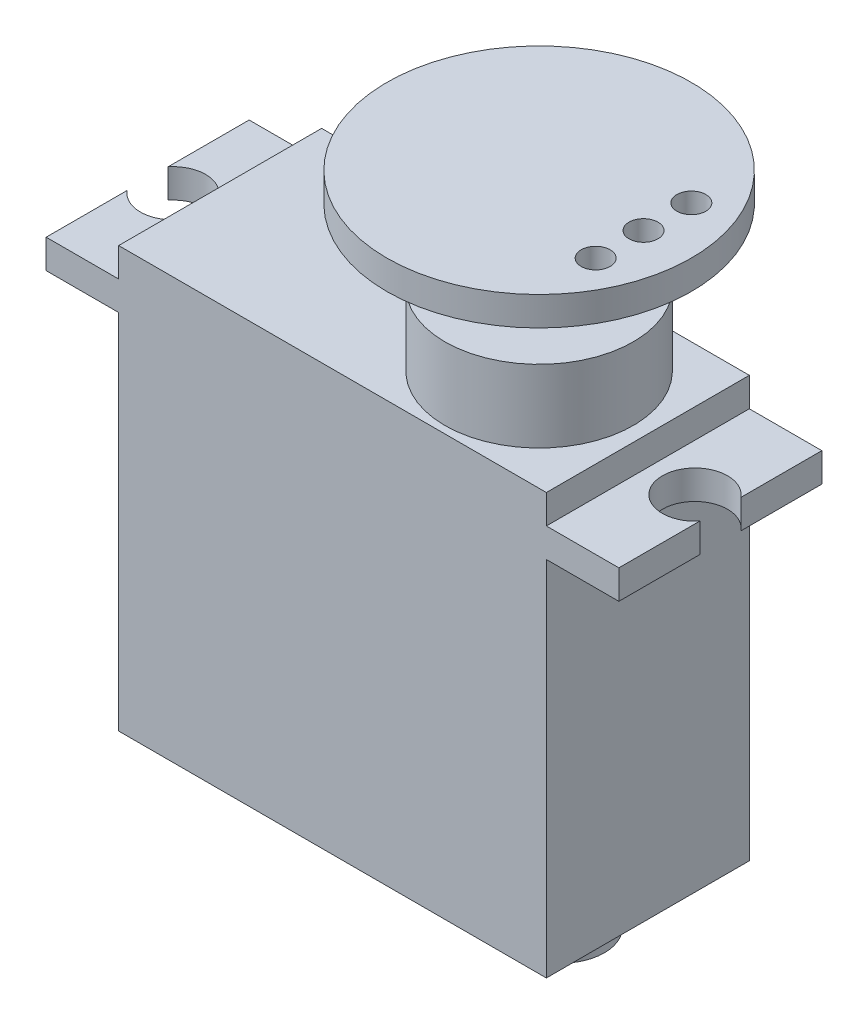
SolidWorks part; units mm, degrees
ref_plane "정면" through (0, 0, 0) normal (0, 0, 1) x (1, 0, 0)
ref_plane "윗면" through (0, 0, 0) normal (0, 1, 0) x (1, 0, 0)
ref_plane "우측면" through (0, 0, 0) normal (1, 0, 0) x (0, 0, -1)
sketch "스케치1" plane through (0, 0, 0) normal (0, 0, 1) x (1, 0, 0)
  line L0 (55, 0) -> (-55, 0) construction
  line L1 (-14.75, 0) -> (14.75, 0)
  line L2 (-14.75, 0) -> (-14.75, -29)
  line L3 (-14.75, -29) -> (14.75, -29)
  line L4 (14.75, 0) -> (14.75, -29)
  point P7 (0, 0)
  dimension "D1" = 29.5
  dimension "D2" = 29
extrude "보스-돌출1" add sketch "스케치1" along normal mid plane 14
ref_plane "평면1" through (0, -2, 0) normal (0, 1, 0) x (1, 0, 0)
sketch "스케치2" plane through (0, -2, 0) normal (0, 1, 0) x (1, 0, 0)
  line L1 (14.75, 7) -> (19.75, 7)
  line L2 (14.75, 7) -> (14.75, -7)
  line L3 (14.75, -7) -> (19.75, -7)
  line L4 (19.75, 7) -> (19.75, -7)
  dimension "D1" = 5
extrude "보스-돌출2" add sketch "스케치2" against normal blind 2
sketch "스케치3" plane through (0, -2, 0) normal (0, 1, 0) x (1, 0, 0)
  line L0 (19.75, -7) -> (19.75, 7) construction
  circle A0 centre (18, 0) radius 2.25
  dimension "D1" = 4.5
  dimension "D2" = 1.75
extrude "컷-돌출1" cut sketch "스케치3" against normal through all
sketch "스케치4" plane through (0, 0, 0) normal (0, 1, 0) x (1, 0, 0)
  line L0 (14.75, -7) -> (14.75, 7) construction
  circle A0 centre (7.25, 0) radius 6.5
  circle A1 centre (7.25, 0) radius 10.5
  circle A2 centre (7.25, 0) radius 2.5
  dimension "D1" = 13
  dimension "D3" = 21
  dimension "D4" = 5
  dimension "D2" = 7.5
extrude "보스-돌출3" add sketch "스케치4" along normal blind 5 contours A0 region at (0.9338, 0, 0)
mirror "대칭 복사1" about plane through (0, 0, 0) normal (1, 0, 0) of "컷-돌출1", "보스-돌출2"
sketch "스케치5" plane through (0, -29, 0) normal (0, -1, 0) x (1, 0, 0)
  line L0 (14.75, 7) -> (14.75, -7) construction
  line L1 (15.95, 0) -> (-15.95, 0) construction
  circle A0 centre (8.75, 0) radius 3
  dimension "D1" = 6
  dimension "D2" = 6
extrude "보스-돌출4" add sketch "스케치5" along normal blind 3.5
extrude "보스-돌출5" add sketch "스케치4<3>" along normal blind 2 from offset 10 separate body contours A1
sketch "스케치4<3>" plane through (0, 0, 0) normal (0, 1, 0) x (1, 0, 0) same geometry as "스케치4"
extrude "보스-돌출6" add sketch "스케치4<4>" along normal up to surface (10 mm away) contours A2 up to face at (7.25, 10, 10.5)
sketch "스케치4<4>" plane through (0, 0, 0) normal (0, 1, 0) x (1, 0, 0) same geometry as "스케치4"
sketch "스케치6" plane through (0, 12, 0) normal (0, 1, 0) x (1, 0, 0)
  line L0 (-21.725, 0) -> (21.725, 0) construction
  circle A0 centre (14.45, 0) radius 1
  circle A1 centre (7.25, 0) radius 10.5 construction
  circle A2 centre (14.45, 3.3) radius 1
  circle A3 centre (14.45, -3.3) radius 1
  dimension "D2" = 2
  dimension "D4" = 2
  dimension "D1" = 7.2
  dimension "D3" = 3.3
extrude "컷-돌출2" cut sketch "스케치6" against normal up to next contours A2 | A0 | A3 region at (14.45, 12, 0) region at (14.45, 12, -3.3) region at (14.45, 12, 3.3)
